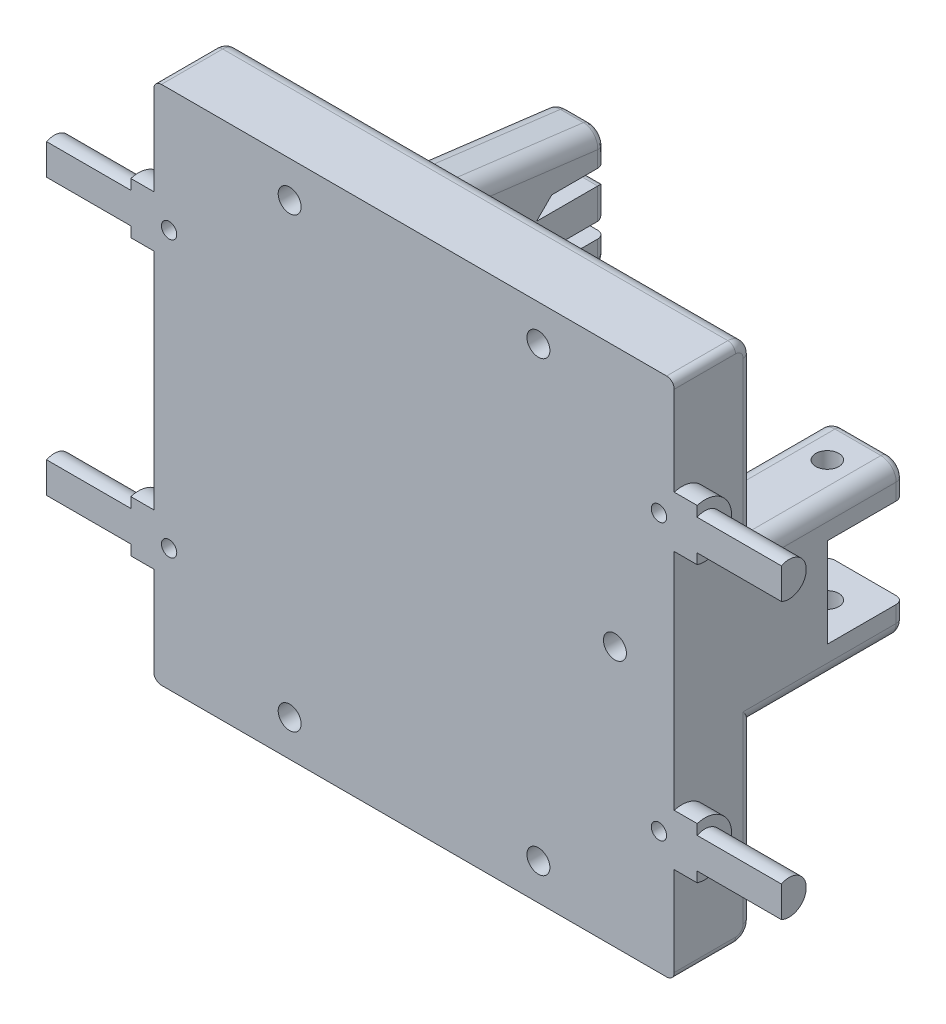
SolidWorks part; units mm, degrees
ref_plane "Front Plane" through (0, 0, 0) normal (0, 0, 1) x (1, 0, 0)
ref_plane "Top Plane" through (0, 0, 0) normal (0, 1, 0) x (1, 0, 0)
ref_plane "Right Plane" through (0, 0, 0) normal (1, 0, 0) x (0, 0, -1)
sketch "Sketch1" plane through (0, 0, 0) normal (0, 0, 1) x (1, 0, 0)
  line L1 (0, 0) -> (-68, 0)
  line L2 (0, 0) -> (0, -68)
  line L3 (0, -68) -> (-68, -68)
  line L4 (-68, 0) -> (-68, -68)
  dimension "D1" = 68
  dimension "D2" = 68
extrude "Boss-Extrude1" add sketch "Sketch1" along normal blind 10
sketch "Sketch2" plane through (-68, 0, 0) normal (-1, 0, 0) x (0, 0, 1)
  line L1 (10, 0) -> (0, 0) construction
  line L2 (10, -68) -> (0, -68) construction
  line L3 (10, 0) -> (10, -68) construction
  line L4 (10, 0) -> (10, -68)
  circle A0 centre (9, -52) radius 3.5
  circle A1 centre (9, -16) radius 3.5
  dimension "D1" = 7
  dimension "D2" = 7
  dimension "D3" = 1
  dimension "D4" = 0
  dimension "D5" = 16
  dimension "D6" = 16
extrude "Boss-Extrude2" add sketch "Sketch2" along normal blind 3 contours L4 A1 | L4 A0 region at (-68, -52, 8.0379) region at (-68, -16, 8.0379)
sketch "Sketch3" plane through (-71, 0, 0) normal (-1, 0, 0) x (0, 0, 1)
  line L0 (10, -55.3541) -> (10, -12.6459)
  circle A0 centre (9, -52) radius 2.25
  circle A1 centre (9, -16) radius 2.25
  dimension "D1" = 4.5
  dimension "D2" = 4.5
extrude "Boss-Extrude3" add sketch "Sketch3" along normal blind 11 contours L0 A0 | L0 A1 region at (-71, -52, 8.5562) region at (-71, -16, 8.5562)
sketch "Sketch4" plane through (0, 0, 0) normal (1, 0, 0) x (0, 0, -1)
  line L0 (-10, 0) -> (0, 0) construction
  line L1 (-10, -68) -> (0, -68) construction
  line L2 (-10, 0) -> (-10, -68)
  circle A0 centre (-9, -16) radius 3.5
  circle A1 centre (-9, -52) radius 3.5
  dimension "D1" = 16
  dimension "D2" = 16
  dimension "D3" = 7
  dimension "D4" = 7
  dimension "D5" = 1
  dimension "D6" = 0
extrude "Boss-Extrude4" add sketch "Sketch4" along normal blind 3 contours L2 A0 | L2 A1 region at (0, -16, 8.0379) region at (0, -52, 8.0379)
sketch "Sketch5" plane through (3, 0, 0) normal (1, 0, 0) x (0, 0, -1)
  line L0 (-10, -12.6459) -> (-10, -55.3541)
  circle A0 centre (-9, -16) radius 2.25
  circle A1 centre (-9, -52) radius 2.25
  dimension "D1" = 4.5
  dimension "D2" = 4.5
extrude "Boss-Extrude5" add sketch "Sketch5" along normal blind 11 contours L0 A0 | L0 A1 region at (3, -16, 8.5562) region at (3, -52, 8.5562)
sketch "Sketch6" plane through (0, 0, 0) normal (0, 0, -1) x (-1, 0, 0)
  line L0 (0, -34) -> (68, -34) construction
  line L1 (55.25, -12.75) -> (12.75, -12.75)
  line L2 (55.25, -12.75) -> (55.25, -55.25)
  line L3 (55.25, -55.25) -> (12.75, -55.25)
  line L4 (12.75, -12.75) -> (12.75, -55.25)
  line L5 (0, -68) -> (0, 0) construction
  line L6 (68, 0) -> (68, -68) construction
  line L7 (34, 0) -> (34, -68) construction
  line L8 (0, 0) -> (68, 0) construction
  line L9 (68, -68) -> (0, -68) construction
  point P16 (12.75, -34)
  point P17 (34, -55.25)
  dimension "D1" = 42.5
  dimension "D2" = 42.5
  dimension "D3" = 0
  dimension "D4" = 0
extrude "Cut-Extrude1" cut sketch "Sketch6" against normal blind 3
sketch "Sketch8" plane through (0, 0, 0) normal (0, 0, -1) x (-1, 0, 0)
  line L0 (55.25, -12.75) -> (12.75, -12.75) construction
  line L2 (12.75, -12.75) -> (12.75, -55.25) construction
  line L3 (34, 0) -> (34, -108.8236) construction
  line L4 (0, 0) -> (68, 0) construction
  line L5 (0, -34) -> (112.3527, -34) construction
  line L6 (0, -68) -> (0, 0) construction
  circle A0 centre (17.75, -4.75) radius 1.5
  circle A3 centre (50.25, -4.75) radius 1.5
  circle A4 centre (50.25, -63.25) radius 1.5
  circle A5 centre (17.75, -63.25) radius 1.5
  dimension "D1" = 8
  dimension "D3" = 3
  dimension "D5" = 5
extrude "Cut-Extrude2" cut sketch "Sketch8" against normal blind 15
sketch "Sketch9" plane through (0, 0, 0) normal (0, 0, -1) x (-1, 0, 0)
  line L1 (0, -24) -> (10, -24)
  line L2 (0, -24) -> (0, -44)
  line L3 (0, -44) -> (10, -44)
  line L4 (10, -24) -> (10, -44)
  line L6 (0, -68) -> (0, 0) construction
  point P4 (0, -34)
  point P7 (0, -34)
  dimension "D1" = 0
  dimension "D2" = 20
  dimension "D3" = 0
  dimension "D4" = 10
  dimension "D5" = 90
  dimension "D6" = 90
  dimension "D7" = 90
extrude "Boss-Extrude6" add sketch "Sketch9" along normal blind 20
sketch "Sketch10" plane through (0, 0, 0) normal (0, 0, -1) x (-1, 0, 0)
  line L0 (0, -56) -> (23.3312, -56) construction
  line L1 (0, -68) -> (0, -44) construction
  line L2 (12.75, -12.75) -> (12.75, -55.25) construction
  line L3 (10, -44) -> (10, -24) construction
  circle A0 centre (7.75, -34) radius 1.5
  circle A1 centre (7.75, -78) radius 1.5
  point P10 (10, -34)
  dimension "D1" = 3
  dimension "D2" = 5
  dimension "D3" = 0
extrude "Cut-Extrude3" cut sketch "Sketch10" against normal blind 10
sketch "Sketch11" plane through (0, 0, 10) normal (0, 0, 1) x (1, 0, 0)
  line L0 (-68, -34) -> (19.7059, -34) construction
  line L1 (-68, -19.3541) -> (-68, -48.6459) construction
  line L2 (-34, -68) -> (-34, 32.0149) construction
  line L3 (-68, -68) -> (0, -68) construction
  line L4 (-82, -54.0156) -> (-82, -49.9844) construction
  circle A0 centre (-66, -52) radius 1
  circle A1 centre (-66, -16) radius 1
  circle A2 centre (-2, -52) radius 1
  circle A3 centre (-2, -16) radius 1
  point P12 (-82, -52)
  dimension "D1" = 16
  dimension "D2" = 0
  dimension "D3" = 2
extrude "Cut-Extrude4" cut sketch "Sketch11" against normal blind 20
sketch "Sketch13" plane through (0, 0, 0) normal (0, 0, -1) x (-1, 0, 0)
  line L0 (68, 0) -> (68, -68) construction
  line L1 (59, -26) -> (66, -26)
  line L2 (59, -26) -> (59, -42)
  line L3 (59, -42) -> (66, -42)
  line L4 (66, -26) -> (66, -42)
  point P4 (66, -34)
  point P7 (68, -34)
  dimension "D1" = 7
  dimension "D2" = 0
  dimension "D3" = 16
  dimension "D4" = 2
extrude "Boss-Extrude7" add sketch "Sketch13" along normal blind 40
sketch "Sketch15" plane through (-66, 0, 0) normal (-1, 0, 0) x (0, 0, 1)
  line L0 (-40, -34) -> (24.0661, -34) construction
  line L1 (-40, -42) -> (-40, -26) construction
  line L2 (-40, -32) -> (-31, -32)
  line L3 (-31, -32) -> (-33, -30)
  line L4 (-33, -30) -> (-40, -30)
  line L5 (-40, -30) -> (-40, -32)
  line L6 (-40, -26) -> (0, -26) construction
  line L7 (-40, -38) -> (-40, -36)
  line L8 (-31, -36) -> (-33, -38)
  line L9 (-33, -38) -> (-40, -38)
  line L10 (-40, -36) -> (-31, -36)
  dimension "D1" = 2
  dimension "D2" = 4
  dimension "D3" = 45
  dimension "D4" = 7
extrude "Cut-Extrude5" cut sketch "Sketch15" against normal blind 10
sketch "Sketch16" plane through (-66, 0, 0) normal (-1, 0, 0) x (0, 0, 1)
  line L0 (0, -26) -> (-40, -26)
  line L1 (-40, -26) -> (0, -21)
  line L2 (0, -21) -> (0, -26)
  line L3 (-40, -34) -> (21.219, -34) construction
  line L4 (-40, -36) -> (-40, -32) construction
  line L5 (-40, -42) -> (0, -47)
  line L6 (0, -42) -> (-40, -42)
  line L7 (0, -47) -> (0, -42)
  dimension "D1" = 5
extrude "Boss-Extrude8" add sketch "Sketch16" against normal up to vertex (7 mm away) up to point (-59, -26, -40)
sketch "Sketch17" plane through (0, 0, -20) normal (0, 0, -1) x (-1, 0, 0)
  line L1 (0, -28.15) -> (10, -28.15)
  line L2 (0, -28.15) -> (0, -39.85)
  line L3 (0, -39.85) -> (10, -39.85)
  line L4 (10, -28.15) -> (10, -39.85)
  line L5 (10, -44) -> (10, -24) construction
  line L6 (0, -24) -> (0, -44) construction
  point P4 (0, -34)
  point P9 (0, -34)
  dimension "D1" = 0
  dimension "D2" = 11.7
  dimension "D3" = 0
extrude "Cut-Extrude6" cut sketch "Sketch17" against normal blind 10
sketch "Sketch18" plane through (0, -44, 0) normal (0, -1, 0) x (-1, 0, 0)
  line L0 (0, 20) -> (10, 20) construction
  line L1 (0, 10) -> (0, 20) construction
  circle A0 centre (5, 15) radius 1.5
  point P4 (5, 20)
  point P7 (0, 15)
  dimension "D1" = 0
  dimension "D2" = 0
  dimension "D3" = 3
extrude "Cut-Extrude7" cut sketch "Sketch18" against normal blind 30
fillet "Fillet2" radius 2 10 edges at (-10, -44, -10) (0, -44, -10) (0, -24, -10) (-10, -24, -10) (-59, -23.5, -20) (-66, -23.5, -20) (-59, -44.5, -20) (-66, -44.5, -20) (-34, 0, 0) (-34, -68, 0)
fillet "Fillet3" radius 1 35 edges at (-59, -38.9922, -40) (-59.5858, -41.4097, -40) (-66, -38.9922, -40) (-65.4142, -41.4097, -40) (-66, -29.0078, -40) (-65.4142, -26.5903, -40) (-59, -29.0078, -40) (-59.5858, -26.5903, -40) (0, -40.925, -20) (-0.5858, -43.4142, -20) (-10, -40.925, -20) (-9.4142, -43.4142, -20) (-10, -27.075, -20) (-9.4142, -24.5858, -20) (0, -27.075, -20) (-0.5858, -24.5858, -20) (-68, 0, 6) (-68, -0.5858, 0.5858) (-68, -68, 6) (-68, -67.4142, 0.5858) (0, -68, 6) (0, -67.4142, 0.5858) (0, 0, 6) (0, -0.5858, 0.5858) (-59, -34, -40) (-62.5, -36, -40) (-66, -34, -40) (-62.5, -32, -40) (-62.5, -42, -40) (-62.5, -26, -40) (-5, -44, -20) (-5, -24, -20) (-68, -34, 0) (0, -54, 0) (0, -14, 0)
